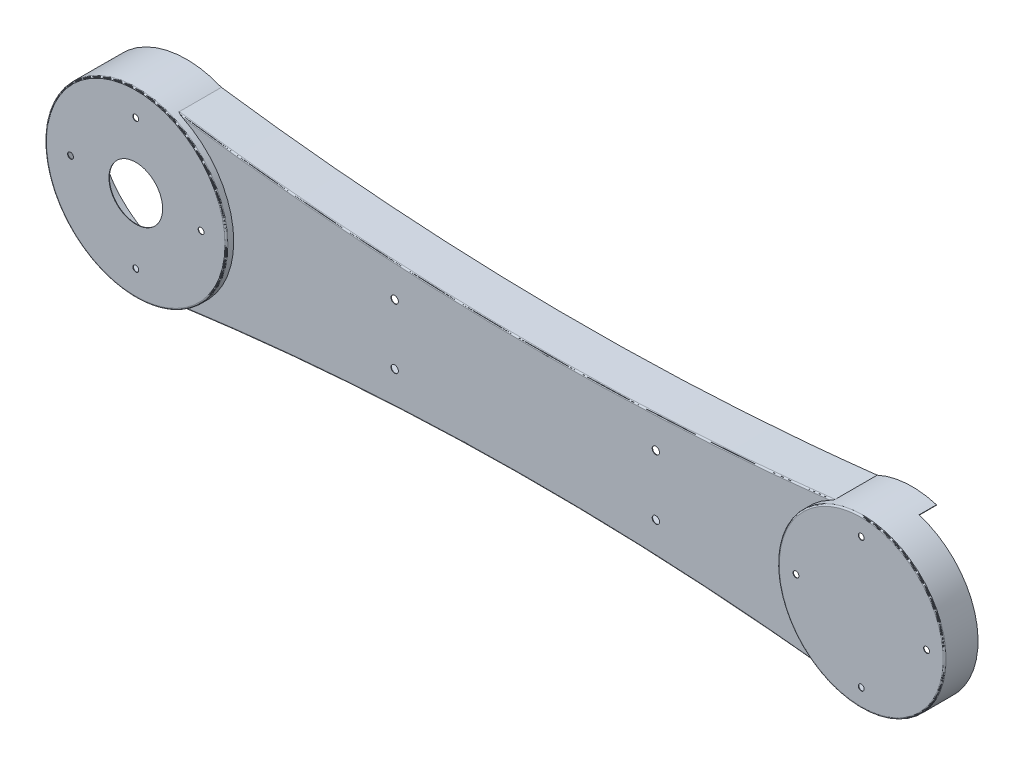
SolidWorks part; units mm, degrees
ref_plane "Front Plane" through (0, 0, 0) normal (0, 0, 1) x (1, 0, 0)
ref_plane "Top Plane" through (0, 0, 0) normal (0, 1, 0) x (1, 0, 0)
ref_plane "Right Plane" through (0, 0, 0) normal (1, 0, 0) x (0, 0, -1)
sketch "Sketch1" plane through (0, 0, 0) normal (0, 0, 1) x (1, 0, 0)
  line L0 (0, 0) -> (500, 0) construction
  line L1 (250, 0) -> (250, 152.9832) construction
  line L2 (24, 57.7083) -> (24, -57.7083) construction
  line L3 (476, 52.2518) -> (476, -52.2518) construction
  line L4 (0, 0) -> (0, 78.9019) construction
  circle A0 centre (0, 0) radius 62.5
  circle A1 centre (500, 0) radius 57.5
  spline S0 degree 2 poles (24, 57.7083) (249.6559, 26.362) (476, 52.2518) knots 0 0 0 1 1 1
  spline S1 degree 2 poles (24, -57.7083) (249.6559, -26.362) (476, -52.2518) knots 0 0 0 1 1 1
  dimension "D1" = 125
  dimension "D3" = 115
  dimension "D2" = 500
  dimension "D4" = 24
extrude "Boss-Extrude1" add sketch "Sketch1" along normal blind 35 contours A0 | A1 region at (0, 0, 0) region at (500, 0, 0)
extrude "Boss-Extrude2" add sketch "Sketch1<3>" along normal blind 30 contours A0 A1 region at (248.7459, 0, 0)
sketch "Sketch1<3>" plane through (0, 0, 0) normal (0, 0, 1) x (1, 0, 0) same geometry as "Sketch1"
shell "Shell1" thickness 0.3 removed face at (135.75, 0, 0)
sketch "Sketch2" plane through (0, 0, 34.7) normal (0, 0, -1) x (-1, 0, 0)
  circle A0 centre (0, 0) radius 57.5
  dimension "D1" = 115
sketch "Sketch3" plane through (0, 0, 34.7) normal (0, 0, -1) x (-1, 0, 0)
  circle A1 centre (0, 0) radius 62.5
  circle A2 centre (-500, 0) radius 57.5
  dimension "D1" = 125
  dimension "D2" = 115
fillet "Fillet1" radius 1 4 edges at (557.5, 0, 35) (62.5, 0, 35)
hole_wizard "Ø4.0mm Dowel Hole1" positions "Sketch4" profile "Sketch5" hole size "Ø4.0" standard "ISO"
sketch "Sketch4" plane through (0, 0, 35) normal (0, 0, 1) x (1, 0, 0)
  line L0 (0, 0) -> (0, 45) construction
  circle A0 centre (0, 0) radius 45 construction
  circle A1 centre (500, 0) radius 45 construction
  point P2 (0, 45)
  point P16 (45, 0)
  point P17 (0, -45)
  point P18 (-45, 0)
  point P24 (500, 45)
  point P29 (545, 0)
  point P30 (500, -45)
  point P31 (455, 0)
  dimension "D1" = 90
  dimension "D3" = 90
  dimension "D2" = 4
  dimension "D4" = 4
sketch "Sketch5" plane through (455, 0, 35) normal (1, 0, 0) x (0, -1, 0)
  line L0 (0, 0) -> (0, 6)
  line L1 (0, 6) -> (2, 4.7983)
  line L2 (2, 4.7983) -> (2, 0.025)
  line L3 (2, 0.025) -> (2.025, 0)
  line L5 (2.025, 0) -> (0, 0)
  line L6 (-2, 0.025) -> (-2.025, 0) construction
  line L10 (0, 6) -> (-2, 4.7983) construction
  line L11 (0, -6.35) -> (0, 107.95) construction
  dimension "Hole Dia." = 4
  dimension "Hole Depth" = 6
  dimension "Near C'Sink Dia." = 4.05
  dimension "Near C'Sink Angle" = 90
  dimension "Drill Angle" = 118
sketch "Sketch6" plane through (0, 0, 0) normal (0, 0, -1) x (-1, 0, 0)
  line L0 (-516.8509, 54.9754) -> (-500, -57.5)
  arc A0 (-476, 52.2518) -> (-476, -52.2518) centre (-500, 0) ccw construction
  arc A1 (-516.8509, 54.9754) -> (-500, -57.5) centre (-500, 0) ccw
extrude "Cut-Extrude1" cut sketch "Sketch6" against normal blind 12
sketch "Sketch7" plane through (0, 0, 35) normal (0, 0, 1) x (1, 0, 0)
  circle A0 centre (0, 0) radius 18.5
  dimension "D1" = 37
extrude "Cut-Extrude2" cut sketch "Sketch7" against normal blind 10
sketch "Sketch10" plane through (0, 0, 30) normal (0, 0, 1) x (1, 0, 0)
  circle A0 centre (353.4315, 20.7143) radius 2.525
  circle A1 centre (173.4315, 20.7143) radius 2.525
  circle A2 centre (353.4315, -20.7143) radius 2.525
  circle A3 centre (173.4315, -20.7143) radius 2.525
extrude "Cut-Extrude3" cut sketch "Sketch10" against normal blind 52.6
